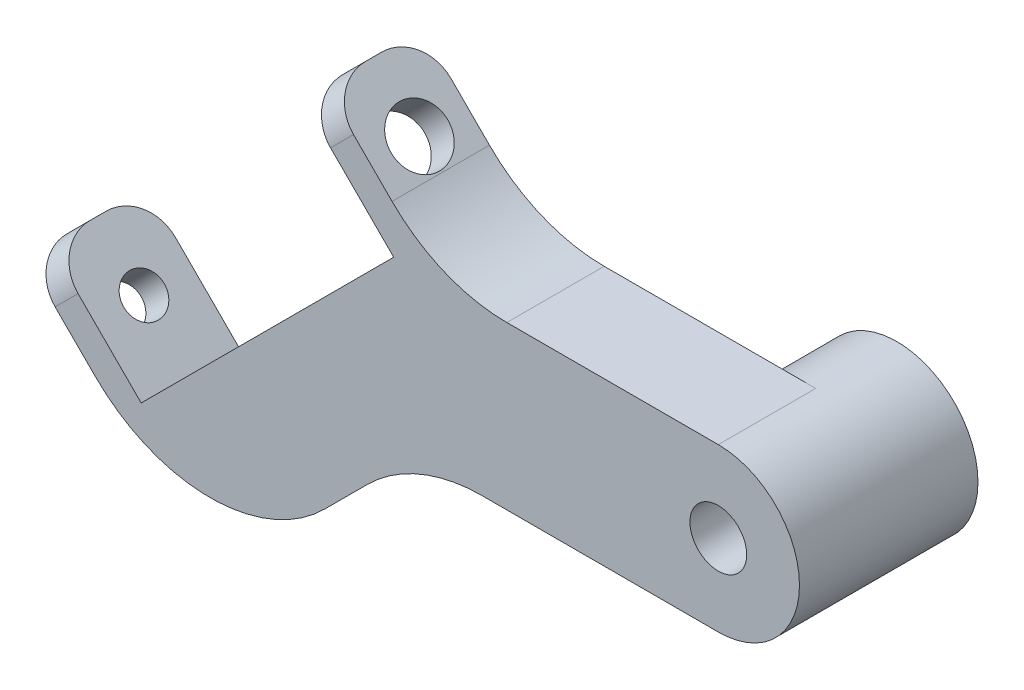
SolidWorks part; units mm, degrees
material "PET"
ref_plane "Piano frontale" through (0, 0, 0) normal (0, 0, 1) x (1, 0, 0)
ref_plane "Piano superiore" through (0, 0, 0) normal (0, 1, 0) x (1, 0, 0)
ref_plane "Piano destro" through (0, 0, 0) normal (1, 0, 0) x (0, 0, -1)
sketch "Schizzo1" plane through (0, 0, 0) normal (0, 0, 1) x (1, 0, 0)
  line L0 (0, 0) -> (-20, 0)
  line L1 (-20, 0) -> (-10, 10)
  line L2 (-10, 10) -> (10, 10)
  line L4 (10, 0) -> (0, 0)
  arc A0 (10, 0) -> (10, 10) centre (10, 5) ccw
  dimension "D6" = 10
  dimension "D1" = 20
  dimension "D2" = 10
  dimension "D3" = 10
  dimension "D4" = 0
  dimension "D5" = 20
extrude "Estrusione-Estrusione1" add sketch "Schizzo1" along normal blind 6 contours L2 A0 L4 L0 L1
sketch "Schizzo3" plane through (0, 0, 6) normal (0, 0, 1) x (1, 0, 0)
  arc A0 (10, 0) -> (10, 10) centre (10, 5) ccw construction
  arc A1 (10, 0) -> (10, 10) centre (10, 5) ccw construction
  circle A2 centre (10, 5) radius 5
  circle A3 centre (10, 5) radius 2.65
  dimension "D1" = 5.3
extrude "Estrusione-Estrusione3" add sketch "Schizzo3" against normal blind 11
sketch "Schizzo4" plane through (0, 0, 6) normal (0, 0, 1) x (1, 0, 0)
  line L0 (-10, 10) -> (-16.0795, 16.0795)
  line L1 (-20, 0) -> (-10, 10) construction
ref_plane "Piano1" through (0, 0, 0) normal (0.7071, 0.7071, 0) x (-0.7071, 0.7071, 0)
sketch "Schizzo5" plane through (0, 0, 0) normal (0.7071, 0.7071, 0) x (-0.7071, 0.7071, 0)
  line L0 (14.1421, 3) -> (18.1421, 3)
  line L1 (14.1421, 6) -> (14.1421, 0) construction
  circle A0 centre (18.1421, 3) radius 0.925
  dimension "D2" = 1.85
  dimension "D1" = 4
extrude "Estrusione-Estrusione4" add sketch "Schizzo5" against normal blind 20 separate body contours A0 region at (-12.8284, 12.8284, 2.1012)
sketch "Schizzo12" plane through (0, 0, 0) normal (0.7071, 0.7071, 0) x (-0.7071, 0.7071, 0)
  line L0 (14.1421, 0) -> (0, 0) construction
  line L1 (14.1421, 6) -> (22.1421, 6)
  line L2 (14.1421, 6) -> (14.1421, 0)
  line L3 (14.1421, 0) -> (22.1421, 0)
  line L4 (22.1421, 6) -> (22.1421, 0)
  dimension "D1" = 8
extrude "Estrusione-Estrusione6" add sketch "Schizzo12" along normal blind 2
sketch "Schizzo13" plane through (-10, 10, 0) normal (0.7071, -0.7071, 0) x (0, 0, -1)
  line L4 (-6, 0) -> (0, 0)
  line L5 (0, 0) -> (0, 2)
  line L6 (0, 2) -> (-6, 2)
  line L7 (-6, 2) -> (-6, 0)
  line L8 (-6, 0) -> (0, 0)
  line L9 (0, 0) -> (0, 2)
  line L10 (0, 2) -> (-6, 2)
  line L11 (-6, 2) -> (-6, 0)
  dimension "D1" = 0
extrude "Estrusione-Estrusione7" add sketch "Schizzo13" along normal blind 3
fillet "Raccordo2" radius 2.5 2 edges at (-14.9497, 16.364, 0) (-14.9497, 16.364, 6)
sketch "Schizzo14" plane through (1.4142, 1.4142, 0) normal (0.7071, 0.7071, 0) x (0, 0, -1)
  circle A0 centre (-3, 18.1421) radius 1.75
  circle A1 centre (-3, 18.1421) radius 0.925
  circle A2 centre (-3, 18.1421) radius 0.925
  dimension "D2" = 3.5
  dimension "D1" = 0
extrude "Taglio-Estrusione7" cut sketch "Schizzo14" against normal blind 25 contours A2 | A0 A2 | A2 | A0 region at (-11.4142, 14.2426, 4.7005) region at (-11.4142, 14.2426, 3)
sketch "Schizzo15" plane through (0, 0, 0) normal (-0.7071, -0.7071, 0) x (0, 0, 1)
  line L0 (0, 14.1421) -> (0, 19.6421) construction
  line L1 (6, 14.1421) -> (0, 14.1421)
  line L2 (6, 14.1421) -> (6, 6.1421)
  line L3 (6, 6.1421) -> (0, 6.1421)
  line L4 (0, 14.1421) -> (0, 6.1421)
  dimension "D1" = 8
extrude "Estrusione-Estrusione8" add sketch "Schizzo15" along normal blind 24
sketch "Schizzo16" plane through (-10, 10, 0) normal (-0.7071, 0.7071, 0) x (0, 0, 1)
  line L0 (0, -24) -> (0, 0) construction
  line L1 (6, -24) -> (0, -24)
  line L2 (6, -24) -> (6, -22)
  line L3 (6, -22) -> (0, -22)
  line L4 (0, -24) -> (0, -22)
  dimension "D1" = 2
extrude "Estrusione-Estrusione9" add sketch "Schizzo16" along normal up to vertex (8 mm away) up to point (-15.6569, 15.6569, 2.5)
sketch "Schizzo17" plane through (-16.9706, -16.9706, 0) normal (-0.7071, -0.7071, 0) x (0, 0, 1)
  circle A0 centre (3, 18.1421) radius 1.75 construction
  circle A1 centre (3, 18.1421) radius 1.75
  circle A2 centre (3, 18.1421) radius 1.25
  dimension "D1" = 2.5
extrude "Taglio-Estrusione8" cut sketch "Schizzo17" against normal blind 25 contours A2
fillet "Raccordo3" radius 10 1 edges at (-21.3137, -12.6274, 3)
fillet "Raccordo4" radius 10 1 edges at (-8.6863, 0, 3)
fillet "Raccordo5" radius 10 1 edges at (-7.1716, 10, 3)
fillet "Raccordo6" radius 2.5 2 edges at (-31.9203, -0.6066, 0) (-31.9203, -0.6066, 6)
sketch "Schizzo18" plane through (0, 0, 6) normal (0, 0, 1) x (1, 0, 0)
  circle A0 centre (10, 5) radius 1.75
  dimension "D1" = 3.5
extrude "Taglio-Estrusione9" cut sketch "Schizzo18" against normal through all
ref_axis "Assi1" through (-14.0659, 11.591, 3) along (0.7071, 0.7071, 0)
ref_axis "Assi2" through (-13.8891, 13.8891, 6) along (0.7071, -0.7071, 0)
ref_axis "Assi3" through (-10.1005, 12.9289, 6) along (0, 0, -1)
ref_point "Punto1"
ref_point "Punto2"
ref_axis "Assi4" through (10, 5, 0) along (0, 0, -1)
ref_axis "Assi5" through (-3.0294, 10, 6) along (1, 0, 0)
ref_point "Punto3"
sketch "Schizzo19" plane through (0, 0, 0) normal (0, 0, -1) x (-1, 0, 0)
  line L0 (-10, 5) -> (19.95, 5)
  dimension "D1" = 29.95
